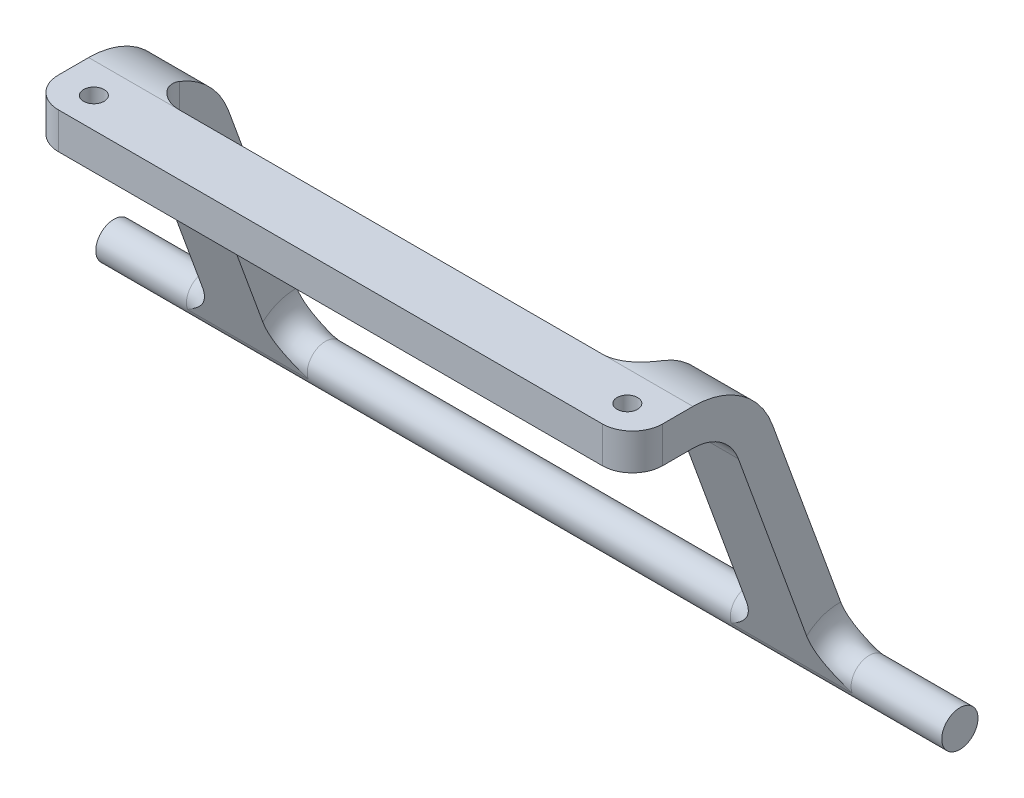
SolidWorks part; units mm, degrees
material "ABS PC"
ref_plane "Front Plane" through (0, 0, 0) normal (0, 0, 1) x (1, 0, 0)
ref_plane "Top Plane" through (0, 0, 0) normal (0, 1, 0) x (1, 0, 0)
ref_plane "Right Plane" through (0, 0, 0) normal (1, 0, 0) x (0, 0, -1)
sketch "Sketch1" plane through (0, 0, 0) normal (0, 1, 0) x (1, 0, 0)
  line L1 (-44.1422, -44.1422) -> (44.1422, -44.1422) construction
  line L2 (-44.1422, -44.1422) -> (-44.1422, 44.1422) construction
  line L3 (-44.1422, 44.1422) -> (44.1422, 44.1422) construction
  line L4 (44.1422, -44.1422) -> (44.1422, 44.1422) construction
  line L5 (-44.1422, -44.1422) -> (44.1422, 44.1422) construction
  line L6 (-44.1422, 44.1422) -> (44.1422, -44.1422) construction
  line L9 (-50, 39.1421) -> (50, 39.1421)
  line L10 (-50, 39.1421) -> (-50, 49.1421)
  line L11 (-50, 49.1421) -> (50, 49.1421)
  line L12 (50, 39.1421) -> (50, 49.1421)
  line L13 (-50, 39.1421) -> (50, 49.1421) construction
  line L14 (-50, 49.1421) -> (50, 39.1421) construction
  circle A0 centre (-44.1422, 44.1422) radius 1.7
  circle A1 centre (44.1422, 44.1422) radius 1.7
  point P0 (0, 0)
  point P8 (0, 44.1422)
  dimension "D2" = 3.4
  dimension "D3" = 3.4
  dimension "D4" = 10
  dimension "D1" = 88.2843
  dimension "D5" = 100
extrude "Boss-Extrude1" add sketch "Sketch1" along normal blind 6
sketch "Sketch3" plane through (50, 0, 0) normal (1, 0, 0) x (0, 0, -1)
  line L0 (49.1421, 6) -> (49.1421, 0) construction
  line L1 (49.1421, -8) -> (49.1421, 0) construction
  line L2 (49.1421, -8) -> (66.0085, -1.8612) construction
  line L3 (56.6597, -5.2638) -> (70.5, -43.2899)
  line L4 (62.2978, -3.2117) -> (76.1382, -41.2378)
  line L5 (71.2185, -45.2638) -> (74.411, -45.2638) construction
  line L6 (49.1421, 6) -> (49.1421, 0)
  arc A0 (49.1421, 0) -> (56.6597, -5.2638) centre (49.1421, -8) cw
  arc A1 (49.1421, 6) -> (62.2978, -3.2117) centre (49.1421, -8) cw
  arc A2 (70.5, -43.2899) -> (76.1382, -41.2378) centre (73.3191, -42.2638) ccw
  dimension "D2" = 70
  dimension "D1" = 8
  dimension "D3" = 40
extrude "Boss-Extrude2" add sketch "Sketch3" against normal blind 10
mirror "Mirror8" about plane through (0, 0, 0) normal (1, 0, 0) of "Boss-Extrude2"
sketch "Sketch5" plane through (50, 0, 0) normal (1, 0, 0) x (0, 0, -1)
  line L0 (70.5, -43.2899) -> (76.1382, -41.2378) construction
  circle A0 centre (73.3191, -42.2638) radius 3
  arc A1 (70.5, -43.2899) -> (76.1382, -41.2378) centre (73.3191, -42.2638) ccw construction
  arc A2 (70.5, -43.2899) -> (76.1382, -41.2378) centre (73.3191, -42.2638) ccw construction
  point P7 (73.3191, -42.2638)
extrude "Boss-Extrude3" add sketch "Sketch5" against normal offset from surface 20 and the other way blind 20 up to face at (-50, -10.0704, -55.6841) offset beyond the face yes
fillet "Fillet1" radius 5 4 edges at (-40, -39.4448, -72.2931) (40, -39.4448, -72.2931) (-50, -39.4448, -72.2931) (50, -39.4448, -72.2931)
fillet "Fillet2" radius 5 4 edges at (40, 3, -49.1421) (-40, 3, -49.1421) (-50, 3, -39.1421) (50, 3, -39.1421)
